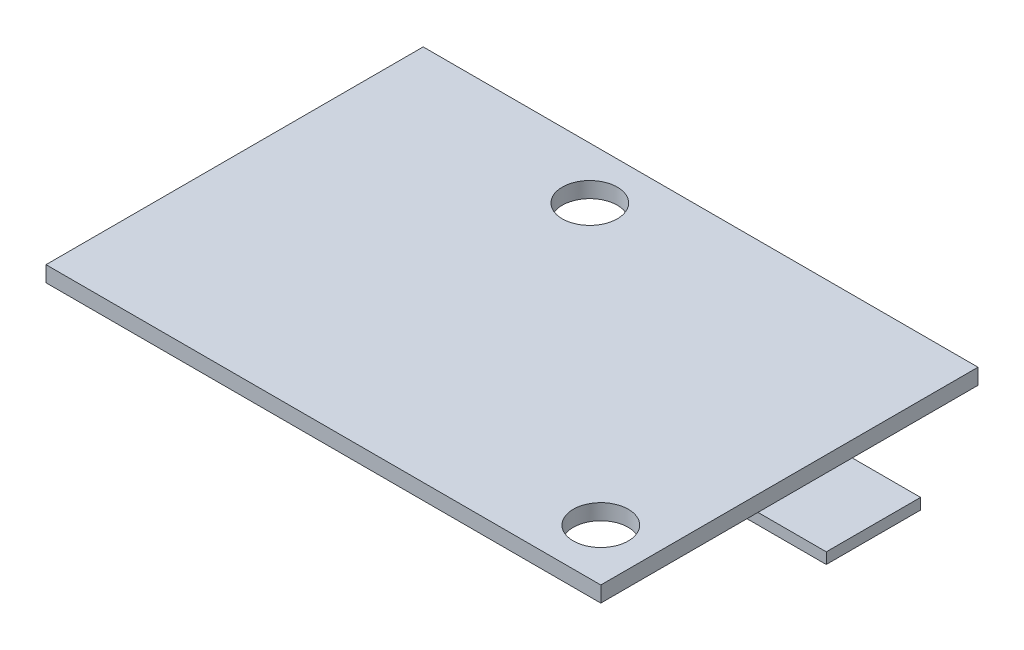
SolidWorks part; units mm, degrees
ref_plane "Спереди" through (0, 0, 0) normal (0, 0, 1) x (1, 0, 0)
ref_plane "Сверху" through (0, 0, 0) normal (0, 1, 0) x (1, 0, 0)
ref_plane "Справа" through (0, 0, 0) normal (1, 0, 0) x (0, 0, -1)
sketch "Sketch1" plane through (0, 0, 0) normal (0, 1, 0) x (1, 0, 0)
  line L1 (-17.65, -12) -> (17.65, -12)
  line L2 (-17.65, -12) -> (-17.65, 12)
  line L3 (-17.65, 12) -> (17.65, 12)
  line L4 (17.65, -12) -> (17.65, 12)
  line L5 (-17.65, -12) -> (17.65, 12) construction
  line L6 (-17.65, 12) -> (17.65, -12) construction
  point P0 (0, 0)
  dimension "D1" = 35.3
  dimension "D2" = 24
extrude "Boss-Extrude1" add sketch "Sketch1" along normal blind 1
hole_wizard "Ø3.5 (3.5) Diameter Hole1" positions "Sketch3" profile "Sketch4" hole size "Ø3.5" standard "ANSI Metric" end condition up to next
sketch "Sketch3" plane through (0, 1, 0) normal (0, 1, 0) x (1, 0, 0)
  line L0 (17.65, 12) -> (-17.65, 12) construction
  line L3 (-17.65, -12) -> (17.65, -12) construction
  line L4 (17.65, -12) -> (17.65, 12) construction
  point P0 (-3.75, 8.7)
  point P2 (14.35, -8.7)
  dimension "D1" = 3.3
  dimension "D2" = 21.4
  dimension "D3" = 3.3
  dimension "D4" = 3.3
sketch "Sketch4" plane through (-3.75, 1, -8.7) normal (1, 0, 0) x (0, 0, 1)
  line L0 (0, 0) -> (0, 1)
  line L1 (0, 1) -> (1.75, 1)
  line L2 (1.75, 1) -> (1.75, 0)
  line L5 (1.75, 0) -> (0, 0)
  line L11 (0, -6.35) -> (0, 107.95) construction
  dimension "Thru Hole Dia." = 3.5
  dimension "Thru Hole Depth" = 1
sketch "Sketch5" plane through (0, 0, 0) normal (0, -1, 0) x (1, 0, 0)
  line L0 (-17.65, 12) -> (17.65, 12) construction
  line L1 (14.8664, 2) -> (21.996, 2)
  line L2 (14.8664, 2) -> (14.8664, -4)
  line L3 (14.8664, -4) -> (21.996, -4)
  line L4 (21.996, 2) -> (21.996, -4)
  dimension "D1" = 6
  dimension "D2" = 10
extrude "Boss-Extrude2" add sketch "Sketch5" along normal blind 0.7
sketch "Sketch6" plane through (0, 0, 0) normal (0, 1, 0) x (1, 0, 0)
  line L0 (26.0926, 1) -> (50026.0926, 1) construction
  line L1 (21.996, 4) -> (21.996, -2) construction
  point P4 (21.996, 1)
ref_plane "Plane1" through (0, 0, -1) normal (0, 0, 1) x (1, 0, 0)
